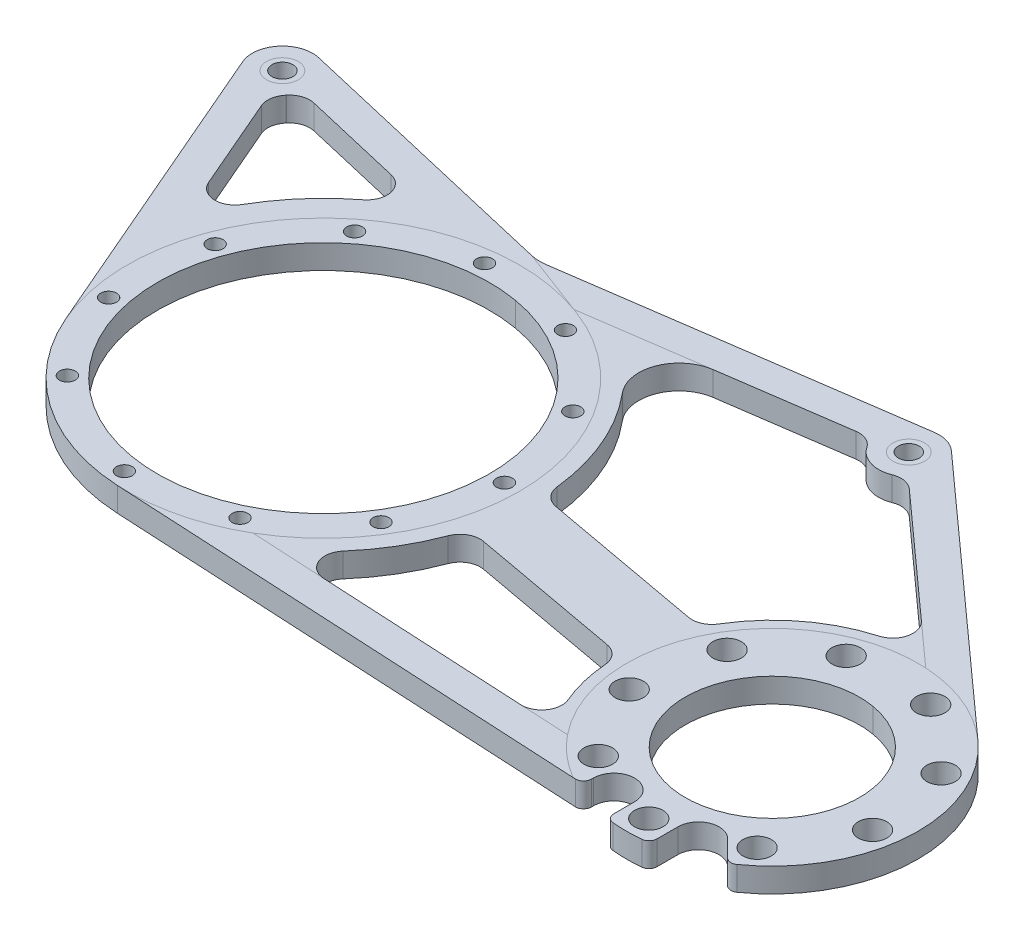
SolidWorks part; units mm, degrees
material "6061-T6 (SS)"
ref_plane "X-Y Datum" through (0, 0, 0) normal (0, 0, 1) x (1, 0, 0)
ref_plane "X-Z Datum" through (0, 0, 0) normal (0, 1, 0) x (1, 0, 0)
ref_plane "Y-Z Datum" through (0, 0, 0) normal (1, 0, 0) x (0, 0, -1)
sketch "Sketch2" plane through (0, 31.3819, 0) normal (0, 1, 0) x (1, 0, 0)
  line L0 (-693.7583, -176.702) -> (-693.7583, -183.2747) construction
  line L1 (-680.0808, -183.2747) -> (-680.0808, -176.702) construction
  line L2 (-668.9846, -172.1058) -> (-663.7197, -177.3707) construction
  line L3 (-693.7583, -176.702) -> (-693.7583, -183.2747)
  line L4 (-680.0808, -183.2747) -> (-680.0808, -176.702)
  line L5 (-668.9846, -172.1058) -> (-663.7197, -177.3707)
  line L6 (-966.641, -0.354) -> (-738.041, -0.354)
  line L7 (-727.7656, -5.5904) -> (-649.7224, -113.0358)
  line L9 (-977.8288, -19.0644) -> (-913.2312, -139.3061)
  line L10 (-706.7583, -177.279) -> (-706.7583, -176.702) construction
  line L11 (-706.7583, -177.279) -> (-706.7583, -176.702)
  line L12 (-861.9259, -171.8334) -> (-709.2983, -179.819)
  line L13 (-858.691, -110.0055) -> (-686.9195, -140.054) construction
  line L14 (-972.26, -24.9963) -> (-955.4664, -39.59) construction
  line L15 (-941.4162, -26.937) -> (-954.1775, -8.712) construction
  line L16 (-751.1929, -14.159) -> (-755.4346, -35.9995) construction
  line L17 (-737.4517, -41.8408) -> (-728.049, -21.6768) construction
  line L18 (-972.26, -24.9963) -> (-955.4664, -39.59)
  line L19 (-941.4162, -26.937) -> (-954.1775, -8.712)
  line L20 (-751.1929, -14.159) -> (-755.4346, -35.9995)
  line L21 (-737.4517, -41.8408) -> (-728.049, -21.6768)
  line L22 (-949.2186, -22.8753) -> (-746.0843, -28.2904)
  line L23 (-739.7146, -30.7335) -> (-656.1751, -105.8723)
  line L24 (-957.9647, -36.1729) -> (-915.5404, -134.527)
  arc A0 (-710.607, -179.4559) -> (-706.7583, -177.279) centre (-709.2983, -177.279) ccw construction
  arc A1 (-693.7583, -176.702) -> (-706.7583, -176.702) centre (-700.2583, -176.702) ccw construction
  arc A2 (-693.7583, -183.2747) -> (-691.4697, -185.8023) centre (-691.2183, -183.2747) ccw construction
  arc A3 (-691.4697, -185.8023) -> (-682.3694, -185.8023) centre (-686.9195, -140.054) ccw construction
  arc A4 (-682.3694, -185.8023) -> (-680.0808, -183.2747) centre (-682.6208, -183.2747) ccw construction
  arc A5 (-668.9846, -172.1058) -> (-680.0808, -176.702) centre (-673.5808, -176.702) ccw construction
  arc A6 (-663.7197, -177.3707) -> (-660.4619, -177.6519) centre (-661.9236, -175.5746) ccw construction
  arc A7 (-660.4619, -177.6519) -> (-710.607, -179.4559) centre (-686.9195, -140.054) ccw construction
  circle A8 centre (-858.691, -110.0055) radius 52.3875 construction
  circle A9 centre (-858.691, -110.0055) radius 61.9125 construction
  circle A10 centre (-738.041, -13.054) radius 12.7 construction
  circle A11 centre (-966.641, -13.054) radius 12.7 construction
  arc A12 (-710.607, -179.4559) -> (-706.7583, -177.279) centre (-709.2983, -177.279) ccw
  arc A13 (-693.7583, -176.702) -> (-706.7583, -176.702) centre (-700.2583, -176.702) ccw
  arc A14 (-693.7583, -183.2747) -> (-691.4697, -185.8023) centre (-691.2183, -183.2747) ccw
  arc A15 (-691.4697, -185.8023) -> (-682.3694, -185.8023) centre (-686.9195, -140.054) ccw
  arc A16 (-682.3694, -185.8023) -> (-680.0808, -183.2747) centre (-682.6208, -183.2747) ccw
  arc A17 (-668.9846, -172.1058) -> (-680.0808, -176.702) centre (-673.5808, -176.702) ccw
  arc A18 (-663.7197, -177.3707) -> (-660.4619, -177.6519) centre (-661.9236, -175.5746) ccw
  arc A19 (-660.4619, -177.6519) -> (-710.607, -179.4559) centre (-686.9195, -140.054) ccw
  circle A20 centre (-858.691, -110.0055) radius 52.3875
  circle A21 centre (-858.691, -110.0055) radius 61.9125
  circle A22 centre (-738.041, -13.054) radius 12.7
  circle A23 centre (-966.641, -13.054) radius 12.7
  circle A31 centre (-864.6648, -166.8424) radius 2.5 construction
  circle A39 centre (-864.6648, -166.8424) radius 2.5
  circle A40 centre (-686.9195, -140.054) radius 27.4955 construction
  circle A41 centre (-686.9195, -140.054) radius 27.4955
  circle A42 centre (-711.9883, -169.9297) radius 4.5 construction
  circle A43 centre (-725.3271, -146.8263) radius 4.5 construction
  circle A44 centre (-720.6945, -120.554) radius 4.5 construction
  circle A45 centre (-700.2583, -103.406) radius 4.5 construction
  circle A46 centre (-673.5808, -103.406) radius 4.5 construction
  circle A47 centre (-653.1446, -120.554) radius 4.5 construction
  circle A48 centre (-648.512, -146.8263) radius 4.5 construction
  circle A49 centre (-661.8508, -169.9297) radius 4.5 construction
  circle A50 centre (-686.9195, -179.054) radius 4.5 construction
  circle A51 centre (-711.9883, -169.9297) radius 4.5
  circle A52 centre (-725.3271, -146.8263) radius 4.5
  circle A53 centre (-720.6945, -120.554) radius 4.5
  circle A54 centre (-700.2583, -103.406) radius 4.5
  circle A55 centre (-673.5808, -103.406) radius 4.5
  circle A56 centre (-653.1446, -120.554) radius 4.5
  circle A57 centre (-648.512, -146.8263) radius 4.5
  circle A58 centre (-661.8508, -169.9297) radius 4.5
  circle A59 centre (-686.9195, -179.054) radius 4.5
  circle A60 centre (-966.641, -13.054) radius 3.3
  circle A61 centre (-738.041, -13.054) radius 3.3
  arc A62 (-955.4664, -39.59) -> (-941.4162, -26.937) centre (-949.2186, -32.4003) ccw construction
  arc A63 (-749.3237, -37.1863) -> (-742.8448, -38.4445) centre (-746.0843, -37.8154) ccw construction
  arc A64 (-742.8448, -38.4445) -> (-749.3237, -37.1863) centre (-746.0843, -37.8154) ccw construction
  arc A65 (-755.4346, -35.9995) -> (-737.4517, -41.8408) centre (-746.0843, -37.8154) ccw construction
  arc A66 (-955.4664, -39.59) -> (-941.4162, -26.937) centre (-949.2186, -32.4003) ccw
  arc A67 (-749.3237, -37.1863) -> (-742.8448, -38.4445) centre (-746.0843, -37.8154) ccw
  arc A68 (-742.8448, -38.4445) -> (-749.3237, -37.1863) centre (-746.0843, -37.8154) ccw
  arc A69 (-755.4346, -35.9995) -> (-737.4517, -41.8408) centre (-746.0843, -37.8154) ccw
  circle A70 centre (-949.2186, -32.4003) radius 3.3
  circle A71 centre (-949.2186, -32.4003) radius 9.525
  circle A72 centre (-746.0843, -37.8154) radius 9.525
  point P94 (-949.2186, -32.4003)
  dimension "D1" = 6.6
  dimension "D2" = 6.6
  dimension "D3" = 6.6
extrude "Boss-Extrude1" add sketch "Sketch2" along normal blind 7.62 contours A21 A39 A20 | A18 A19 A12 L11 A13 L3 A14 A15 A16 L4 A17 L5 A59 A58 A57 A56 A55 A54 A53 A52 A51 A41 | L13 A21 L12 A12 A19 | A21 L13 A19 L23 L21 A69 L20 L22 L19 A66 L18 L24 | A69 A72 A68 A67 | A72 L22 L20 | A72 L21 L23 | A71 L24 L18 | A71 L19 L22 | A71 A66 L22 A70 region at (-700.2583, 31.3819, 168.9016) region at (-773.051, 31.3819, 154.3682) region at (-890.9045, 31.3819, 160.8157) region at (-806.8861, 31.3819, 67.2042) region at (-956.9478, 31.3819, 38.0512) region at (-736.2382, 31.3819, 35.8095) region at (-956.6903, 31.3819, 37.8629) region at (-748.9437, 31.3819, 46.6182) region at (-752.4763, 31.3819, 29.8585) region at (-944.5842, 31.3819, 23.8004)
sketch "Sketch3" plane through (0, 31.3819, 0) normal (0, -1, 0) x (1, 0, 0)
  line L1 (-949.2186, 22.8753) -> (-746.0843, 28.2904) construction
  line L5 (-861.9259, 171.8334) -> (-709.2983, 179.819) construction
  line L6 (-977.8288, 19.0644) -> (-913.2312, 139.3061) construction
  line L7 (-727.7656, 5.5904) -> (-649.7224, 113.0358) construction
  line L13 (-751.1929, 14.159) -> (-755.4346, 35.9995) construction
  line L16 (-966.641, 0.354) -> (-738.041, 0.354) construction
  line L19 (-663.7197, 177.3707) -> (-668.9846, 172.1058)
  line L20 (-680.0808, 176.702) -> (-680.0808, 183.2747)
  line L21 (-693.7583, 183.2747) -> (-693.7583, 176.702)
  line L22 (-706.7583, 176.702) -> (-706.7583, 177.279)
  line L23 (-663.7197, 177.3707) -> (-668.9846, 172.1058)
  line L24 (-680.0808, 176.702) -> (-680.0808, 183.2747)
  line L25 (-693.7583, 183.2747) -> (-693.7583, 176.702)
  line L26 (-706.7583, 176.702) -> (-706.7583, 177.279)
  line L28 (-861.9259, 171.8334) -> (-709.2983, 179.819)
  line L29 (-977.8288, 19.0644) -> (-913.2312, 139.3061)
  line L30 (-727.7656, 5.5904) -> (-649.7224, 113.0358)
  line L31 (-966.641, 0.354) -> (-738.041, 0.354)
  line L34 (-737.4517, 41.8408) -> (-728.049, 21.6768) construction
  line L35 (-972.26, 24.9963) -> (-955.4664, 39.59) construction
  line L36 (-947.0539, 23.1246) -> (-856.9722, 44.1471)
  line L37 (-856.9722, 44.1471) -> (-747.4408, 28.3875)
  line L44 (-941.4162, 26.937) -> (-954.1775, 8.712) construction
  line L45 (-957.9647, 36.1729) -> (-915.5404, 134.527) construction
  line L46 (-739.7146, 30.7335) -> (-656.1751, 105.8723) construction
  line L47 (-861.9259, 171.8334) -> (-709.2983, 179.819)
  line L48 (-977.8288, 19.0644) -> (-913.2312, 139.3061)
  line L49 (-727.7656, 5.5904) -> (-649.7224, 113.0358)
  line L50 (-966.641, 0.354) -> (-738.041, 0.354)
  line L51 (-949.2186, 22.8753) -> (-746.0843, 28.2904)
  line L52 (-751.1929, 14.159) -> (-755.4346, 35.9995)
  line L53 (-737.4517, 41.8408) -> (-728.049, 21.6768)
  line L54 (-972.26, 24.9963) -> (-955.4664, 39.59)
  line L55 (-941.4162, 26.937) -> (-954.1775, 8.712)
  line L56 (-957.9647, 36.1729) -> (-915.5404, 134.527)
  line L57 (-739.7146, 30.7335) -> (-656.1751, 105.8723)
  arc A1 (-737.4517, 41.8408) -> (-755.4346, 35.9995) centre (-746.0843, 37.8154) ccw construction
  circle A3 centre (-966.641, 13.054) radius 12.7
  circle A5 centre (-966.641, 13.054) radius 12.7
  circle A7 centre (-738.041, 13.054) radius 12.7
  circle A9 centre (-738.041, 13.054) radius 12.7
  circle A11 centre (-858.691, 110.0055) radius 61.9125
  circle A13 centre (-858.691, 110.0055) radius 61.9125
  circle A15 centre (-858.691, 110.0055) radius 52.3875
  circle A17 centre (-858.691, 110.0055) radius 52.3875
  circle A19 centre (-686.9195, 140.054) radius 27.4955
  circle A21 centre (-686.9195, 140.054) radius 27.4955
  circle A23 centre (-864.6648, 166.8424) radius 2.5
  circle A25 centre (-864.6648, 166.8424) radius 2.5
  circle A51 centre (-720.6945, 120.554) radius 4.5
  circle A52 centre (-720.6945, 120.554) radius 4.5
  circle A68 centre (-725.3271, 146.8263) radius 4.5
  circle A69 centre (-725.3271, 146.8263) radius 4.5
  circle A70 centre (-711.9883, 169.9297) radius 4.5
  circle A71 centre (-711.9883, 169.9297) radius 4.5
  circle A72 centre (-738.041, 13.054) radius 3.3
  circle A73 centre (-738.041, 13.054) radius 3.3
  circle A74 centre (-966.641, 13.054) radius 3.3
  circle A75 centre (-966.641, 13.054) radius 3.3
  circle A76 centre (-686.9195, 179.054) radius 4.5
  circle A77 centre (-686.9195, 179.054) radius 4.5
  circle A78 centre (-661.8508, 169.9297) radius 4.5
  circle A79 centre (-661.8508, 169.9297) radius 4.5
  circle A80 centre (-648.512, 146.8263) radius 4.5
  circle A81 centre (-648.512, 146.8263) radius 4.5
  circle A82 centre (-653.1446, 120.554) radius 4.5
  circle A83 centre (-653.1446, 120.554) radius 4.5
  circle A84 centre (-673.5808, 103.406) radius 4.5
  circle A85 centre (-673.5808, 103.406) radius 4.5
  circle A86 centre (-700.2583, 103.406) radius 4.5
  circle A87 centre (-700.2583, 103.406) radius 4.5
  arc A95 (-710.607, 179.4559) -> (-660.4619, 177.6519) centre (-686.9195, 140.054) ccw
  arc A96 (-660.4619, 177.6519) -> (-663.7197, 177.3707) centre (-661.9236, 175.5746) ccw
  arc A97 (-680.0808, 176.702) -> (-668.9846, 172.1058) centre (-673.5808, 176.702) ccw
  arc A98 (-680.0808, 183.2747) -> (-682.3694, 185.8023) centre (-682.6208, 183.2747) ccw
  arc A99 (-682.3694, 185.8023) -> (-691.4697, 185.8023) centre (-686.9195, 140.054) ccw
  arc A100 (-691.4697, 185.8023) -> (-693.7583, 183.2747) centre (-691.2183, 183.2747) ccw
  arc A101 (-706.7583, 176.702) -> (-693.7583, 176.702) centre (-700.2583, 176.702) ccw
  arc A102 (-706.7583, 177.279) -> (-710.607, 179.4559) centre (-709.2983, 177.279) ccw
  arc A103 (-710.607, 179.4559) -> (-660.4619, 177.6519) centre (-686.9195, 140.054) ccw
  arc A104 (-660.4619, 177.6519) -> (-663.7197, 177.3707) centre (-661.9236, 175.5746) ccw
  arc A105 (-680.0808, 176.702) -> (-668.9846, 172.1058) centre (-673.5808, 176.702) ccw
  arc A106 (-680.0808, 183.2747) -> (-682.3694, 185.8023) centre (-682.6208, 183.2747) ccw
  arc A107 (-682.3694, 185.8023) -> (-691.4697, 185.8023) centre (-686.9195, 140.054) ccw
  arc A108 (-691.4697, 185.8023) -> (-693.7583, 183.2747) centre (-691.2183, 183.2747) ccw
  arc A109 (-706.7583, 176.702) -> (-693.7583, 176.702) centre (-700.2583, 176.702) ccw
  arc A110 (-706.7583, 177.279) -> (-710.607, 179.4559) centre (-709.2983, 177.279) ccw
  circle A152 centre (-746.0843, 37.8154) radius 9.525
  circle A153 centre (-746.0843, 37.8154) radius 9.525
  circle A154 centre (-949.2186, 32.4003) radius 9.525
  circle A155 centre (-949.2186, 32.4003) radius 9.525
  circle A156 centre (-949.2186, 32.4003) radius 3.3
  circle A157 centre (-949.2186, 32.4003) radius 3.3
  arc A158 (-941.4162, 26.937) -> (-955.4664, 39.59) centre (-949.2186, 32.4003) ccw construction
  arc A159 (-742.8448, 38.4445) -> (-749.3237, 37.1863) centre (-746.0843, 37.8154) ccw
  arc A160 (-749.3237, 37.1863) -> (-742.8448, 38.4445) centre (-746.0843, 37.8154) ccw
  arc A161 (-742.8448, 38.4445) -> (-749.3237, 37.1863) centre (-746.0843, 37.8154) ccw
  arc A162 (-749.3237, 37.1863) -> (-742.8448, 38.4445) centre (-746.0843, 37.8154) ccw
  arc A163 (-737.4517, 41.8408) -> (-755.4346, 35.9995) centre (-746.0843, 37.8154) ccw
  arc A164 (-941.4162, 26.937) -> (-955.4664, 39.59) centre (-949.2186, 32.4003) ccw
  dimension "D24" = 0
  dimension "D25" = 0
  dimension "D26" = 90.0818
  dimension "D27" = 21.0225
  dimension "D1" = 0
  dimension "D2" = 0
  dimension "D3" = 0
  dimension "D4" = 0
  dimension "D5" = 0
  dimension "D6" = 0
  dimension "D14" = 0
  dimension "D15" = 0
  dimension "D16" = 0
  dimension "D17" = 0
  dimension "D18" = 0
  dimension "D19" = 0
  dimension "D20" = 0
  dimension "D21" = 0
  dimension "D22" = 0
  dimension "D23" = 0
  dimension "D52" = 0
  dimension "D53" = 0
  dimension "D54" = 0
  dimension "D55" = 0
ref_point "Point1"
ref_point "Point2"
ref_plane "Plane1" through (-858.691, 31.3819, 110.0055) normal (0.985, 0, 0.1723) x (0.1723, 0, -0.985)
ref_plane "Plane2" through (-686.9195, 31.3819, 140.054) normal (-0.985, 0, -0.1723) x (-0.1723, 0, 0.985)
split line "Split Line1"
split line "Split Line2"
ref_axis "Axis1" through (-858.691, 39.0019, 110.0055) along (0, -1, 0)
ref_axis "Axis2" through (-686.9195, 39.0019, 140.054) along (0, -1, 0)
extrude "Cut-Extrude1" cut sketch "Sketch3" against normal through all contours L36 L55 L51 L52 L37 | A155 L51 L55 L36 | A153 L37 L52 L51 region at (-751.5495, 31.3819, 28.5688) region at (-850.6911, 31.3819, 31.7926) region at (-945.2616, 31.3819, 23.2848)
fillet "Fillet2" radius 12.7 1 edges at (-856.9722, 35.1919, 44.1471)
sketch "Sketch4" plane through (0, 31.3819, 0) normal (0, -1, 0) x (1, 0, 0)
  line L0 (-861.9259, 171.8334) -> (-709.2983, 179.819) construction
  line L1 (-727.7656, 5.5904) -> (-649.7224, 113.0358) construction
  line L2 (-977.8288, 19.0644) -> (-913.2312, 139.3061) construction
  line L4 (-706.7583, 176.702) -> (-706.7583, 177.279)
  line L5 (-663.7197, 177.3707) -> (-668.9846, 172.1058)
  line L6 (-680.0808, 176.702) -> (-680.0808, 183.2747)
  line L7 (-693.7583, 183.2747) -> (-693.7583, 176.702)
  line L8 (-706.7583, 176.702) -> (-706.7583, 177.279)
  line L9 (-663.7197, 177.3707) -> (-668.9846, 172.1058)
  line L10 (-680.0808, 176.702) -> (-680.0808, 183.2747)
  line L11 (-693.7583, 183.2747) -> (-693.7583, 176.702)
  line L13 (-966.641, 0.354) -> (-738.041, 0.354) construction
  line L14 (-861.9259, 171.8334) -> (-709.2983, 179.819)
  line L15 (-727.7656, 5.5904) -> (-649.7224, 113.0358)
  line L16 (-977.8288, 19.0644) -> (-913.2312, 139.3061)
  line L17 (-861.9259, 171.8334) -> (-709.2983, 179.819) construction
  line L19 (-966.641, 0.354) -> (-738.041, 0.354)
  line L20 (-924.6037, 87.863) -> (-948.1369, 33.3048)
  line L21 (-948.1369, 33.3048) -> (-888.5504, 47.2106)
  line L22 (-732.3805, 168.4374) -> (-812.7818, 164.2308) construction
  line L23 (-812.7818, 164.2308) -> (-733.9678, 114.3873) construction
  line L24 (-799.833, 147.0258) -> (-703.8013, 86.2934) construction
  line L25 (-703.8013, 86.2934) -> (-794.9695, 82.1785) construction
  line L26 (-824.108, 49.6832) -> (-755.4008, 39.7974) construction
  line L27 (-798.9847, 74.3695) -> (-701.5009, 78.7695) construction
  line L28 (-701.5009, 78.7695) -> (-739.4428, 44.643) construction
  line L29 (-977.8288, 19.0644) -> (-913.2312, 139.3061) construction
  line L30 (-727.7656, 5.5904) -> (-649.7224, 113.0358) construction
  line L31 (-966.641, 0.354) -> (-738.041, 0.354) construction
  line L32 (-663.7197, 177.3707) -> (-668.9846, 172.1058)
  line L33 (-680.0808, 176.702) -> (-680.0808, 183.2747)
  line L34 (-693.7583, 183.2747) -> (-693.7583, 176.702)
  line L35 (-706.7583, 176.702) -> (-706.7583, 177.279)
  line L36 (-663.7197, 177.3707) -> (-668.9846, 172.1058)
  line L37 (-680.0808, 176.702) -> (-680.0808, 183.2747)
  line L38 (-693.7583, 183.2747) -> (-693.7583, 176.702)
  line L39 (-706.7583, 176.702) -> (-706.7583, 177.279)
  line L40 (-949.2186, 22.8753) -> (-746.0843, 28.2904) construction
  line L41 (-751.1929, 14.159) -> (-755.4346, 35.9995) construction
  line L42 (-737.4517, 41.8408) -> (-728.049, 21.6768) construction
  line L43 (-972.26, 24.9963) -> (-955.4664, 39.59) construction
  line L44 (-941.4162, 26.937) -> (-954.1775, 8.712) construction
  line L45 (-957.9647, 36.1729) -> (-915.5404, 134.527) construction
  line L46 (-739.7146, 30.7335) -> (-656.1751, 105.8723) construction
  line L47 (-861.9259, 171.8334) -> (-709.2983, 179.819)
  line L48 (-977.8288, 19.0644) -> (-913.2312, 139.3061)
  line L49 (-727.7656, 5.5904) -> (-649.7224, 113.0358)
  line L50 (-966.641, 0.354) -> (-738.041, 0.354)
  line L51 (-949.2186, 22.8753) -> (-746.0843, 28.2904)
  line L52 (-751.1929, 14.159) -> (-755.4346, 35.9995)
  line L53 (-737.4517, 41.8408) -> (-728.049, 21.6768)
  line L54 (-972.26, 24.9963) -> (-955.4664, 39.59)
  line L55 (-941.4162, 26.937) -> (-954.1775, 8.712)
  line L56 (-957.9647, 36.1729) -> (-915.5404, 134.527)
  line L57 (-739.7146, 30.7335) -> (-656.1751, 105.8723)
  line L58 (-947.0539, 23.1246) -> (-859.3005, 43.6037) construction
  line L60 (-854.6056, 43.8066) -> (-747.4408, 28.3875) construction
  circle A1 centre (-858.691, 110.0055) radius 52.3875
  circle A2 centre (-858.691, 110.0055) radius 52.3875
  circle A3 centre (-858.691, 110.0055) radius 61.9125
  circle A4 centre (-858.691, 110.0055) radius 61.9125
  circle A5 centre (-738.041, 13.054) radius 12.7
  circle A6 centre (-738.041, 13.054) radius 12.7
  circle A7 centre (-966.641, 13.054) radius 12.7
  circle A8 centre (-966.641, 13.054) radius 12.7
  circle A17 centre (-864.6648, 166.8424) radius 2.5
  circle A18 centre (-864.6648, 166.8424) radius 2.5
  circle A19 centre (-686.9195, 140.054) radius 27.4955
  circle A20 centre (-686.9195, 140.054) radius 27.4955
  circle A21 centre (-725.3271, 146.8263) radius 4.5
  circle A22 centre (-725.3271, 146.8263) radius 4.5
  circle A23 centre (-720.6945, 120.554) radius 4.5
  circle A24 centre (-720.6945, 120.554) radius 4.5
  circle A31 centre (-661.8508, 169.9297) radius 4.5
  circle A32 centre (-661.8508, 169.9297) radius 4.5
  circle A33 centre (-686.9195, 179.054) radius 4.5
  circle A34 centre (-686.9195, 179.054) radius 4.5
  circle A35 centre (-966.641, 13.054) radius 3.3
  circle A36 centre (-966.641, 13.054) radius 3.3
  circle A37 centre (-738.041, 13.054) radius 3.3
  circle A38 centre (-738.041, 13.054) radius 3.3
  circle A39 centre (-711.9883, 169.9297) radius 4.5
  circle A40 centre (-711.9883, 169.9297) radius 4.5
  circle A41 centre (-700.2583, 103.406) radius 4.5
  circle A42 centre (-700.2583, 103.406) radius 4.5
  circle A43 centre (-673.5808, 103.406) radius 4.5
  circle A44 centre (-673.5808, 103.406) radius 4.5
  circle A45 centre (-653.1446, 120.554) radius 4.5
  circle A46 centre (-653.1446, 120.554) radius 4.5
  circle A47 centre (-648.512, 146.8263) radius 4.5
  circle A48 centre (-648.512, 146.8263) radius 4.5
  arc A49 (-888.5504, 47.2106) -> (-924.6037, 87.863) centre (-858.691, 110.0055) cw
  arc A50 (-732.3805, 168.4374) -> (-733.9678, 114.3873) centre (-686.9195, 140.054) ccw construction
  arc A51 (-799.833, 147.0258) -> (-794.9695, 82.1785) centre (-858.691, 110.0055) cw construction
  arc A52 (-824.108, 49.6832) -> (-798.9847, 74.3695) centre (-858.691, 110.0055) ccw construction
  arc A53 (-737.4517, 41.8408) -> (-755.4346, 35.9995) centre (-746.0843, 37.8154) ccw construction
  circle A54 centre (-966.641, 13.054) radius 12.7
  circle A55 centre (-966.641, 13.054) radius 12.7
  arc A56 (-706.7583, 177.279) -> (-710.607, 179.4559) centre (-709.2983, 177.279) ccw
  arc A57 (-710.607, 179.4559) -> (-660.4619, 177.6519) centre (-686.9195, 140.054) ccw
  arc A58 (-660.4619, 177.6519) -> (-663.7197, 177.3707) centre (-661.9236, 175.5746) ccw
  arc A59 (-680.0808, 176.702) -> (-668.9846, 172.1058) centre (-673.5808, 176.702) ccw
  arc A60 (-680.0808, 183.2747) -> (-682.3694, 185.8023) centre (-682.6208, 183.2747) ccw
  arc A61 (-682.3694, 185.8023) -> (-691.4697, 185.8023) centre (-686.9195, 140.054) ccw
  arc A62 (-691.4697, 185.8023) -> (-693.7583, 183.2747) centre (-691.2183, 183.2747) ccw
  arc A63 (-706.7583, 176.702) -> (-693.7583, 176.702) centre (-700.2583, 176.702) ccw
  arc A64 (-706.7583, 177.279) -> (-710.607, 179.4559) centre (-709.2983, 177.279) ccw
  arc A65 (-710.607, 179.4559) -> (-660.4619, 177.6519) centre (-686.9195, 140.054) ccw
  arc A66 (-660.4619, 177.6519) -> (-663.7197, 177.3707) centre (-661.9236, 175.5746) ccw
  arc A67 (-680.0808, 176.702) -> (-668.9846, 172.1058) centre (-673.5808, 176.702) ccw
  arc A68 (-680.0808, 183.2747) -> (-682.3694, 185.8023) centre (-682.6208, 183.2747) ccw
  arc A69 (-682.3694, 185.8023) -> (-691.4697, 185.8023) centre (-686.9195, 140.054) ccw
  arc A70 (-691.4697, 185.8023) -> (-693.7583, 183.2747) centre (-691.2183, 183.2747) ccw
  arc A71 (-706.7583, 176.702) -> (-693.7583, 176.702) centre (-700.2583, 176.702) ccw
  circle A72 centre (-738.041, 13.054) radius 12.7
  circle A73 centre (-738.041, 13.054) radius 12.7
  circle A74 centre (-858.691, 110.0055) radius 61.9125
  circle A75 centre (-858.691, 110.0055) radius 61.9125
  circle A76 centre (-858.691, 110.0055) radius 52.3875
  circle A77 centre (-858.691, 110.0055) radius 52.3875
  circle A78 centre (-686.9195, 140.054) radius 27.4955
  circle A79 centre (-686.9195, 140.054) radius 27.4955
  circle A80 centre (-864.6648, 166.8424) radius 2.5
  circle A81 centre (-864.6648, 166.8424) radius 2.5
  circle A96 centre (-720.6945, 120.554) radius 4.5
  circle A97 centre (-720.6945, 120.554) radius 4.5
  circle A98 centre (-725.3271, 146.8263) radius 4.5
  circle A99 centre (-725.3271, 146.8263) radius 4.5
  circle A100 centre (-711.9883, 169.9297) radius 4.5
  circle A101 centre (-711.9883, 169.9297) radius 4.5
  circle A102 centre (-738.041, 13.054) radius 3.3
  circle A103 centre (-738.041, 13.054) radius 3.3
  circle A104 centre (-966.641, 13.054) radius 3.3
  circle A105 centre (-966.641, 13.054) radius 3.3
  circle A106 centre (-686.9195, 179.054) radius 4.5
  circle A107 centre (-686.9195, 179.054) radius 4.5
  circle A108 centre (-661.8508, 169.9297) radius 4.5
  circle A109 centre (-661.8508, 169.9297) radius 4.5
  circle A110 centre (-648.512, 146.8263) radius 4.5
  circle A111 centre (-648.512, 146.8263) radius 4.5
  circle A112 centre (-653.1446, 120.554) radius 4.5
  circle A113 centre (-653.1446, 120.554) radius 4.5
  circle A114 centre (-673.5808, 103.406) radius 4.5
  circle A115 centre (-673.5808, 103.406) radius 4.5
  circle A116 centre (-700.2583, 103.406) radius 4.5
  circle A117 centre (-700.2583, 103.406) radius 4.5
  circle A118 centre (-746.0843, 37.8154) radius 9.525
  circle A119 centre (-746.0843, 37.8154) radius 9.525
  circle A120 centre (-949.2186, 32.4003) radius 9.525
  circle A121 centre (-949.2186, 32.4003) radius 9.525
  circle A122 centre (-949.2186, 32.4003) radius 3.3
  circle A123 centre (-949.2186, 32.4003) radius 3.3
  arc A124 (-941.4162, 26.937) -> (-955.4664, 39.59) centre (-949.2186, 32.4003) ccw construction
  arc A125 (-742.8448, 38.4445) -> (-749.3237, 37.1863) centre (-746.0843, 37.8154) ccw
  arc A126 (-749.3237, 37.1863) -> (-742.8448, 38.4445) centre (-746.0843, 37.8154) ccw
  arc A127 (-742.8448, 38.4445) -> (-749.3237, 37.1863) centre (-746.0843, 37.8154) ccw
  arc A128 (-749.3237, 37.1863) -> (-742.8448, 38.4445) centre (-746.0843, 37.8154) ccw
  arc A129 (-737.4517, 41.8408) -> (-755.4346, 35.9995) centre (-746.0843, 37.8154) ccw
  arc A130 (-941.4162, 26.937) -> (-955.4664, 39.59) centre (-949.2186, 32.4003) ccw
  arc A135 (-710.607, 179.4559) -> (-660.4619, 177.6519) centre (-686.9195, 140.054) ccw
  arc A136 (-660.4619, 177.6519) -> (-663.7197, 177.3707) centre (-661.9236, 175.5746) ccw
  arc A137 (-680.0808, 176.702) -> (-668.9846, 172.1058) centre (-673.5808, 176.702) ccw
  arc A138 (-680.0808, 183.2747) -> (-682.3694, 185.8023) centre (-682.6208, 183.2747) ccw
  arc A139 (-682.3694, 185.8023) -> (-691.4697, 185.8023) centre (-686.9195, 140.054) ccw
  arc A140 (-691.4697, 185.8023) -> (-693.7583, 183.2747) centre (-691.2183, 183.2747) ccw
  arc A141 (-706.7583, 176.702) -> (-693.7583, 176.702) centre (-700.2583, 176.702) ccw
  arc A142 (-706.7583, 177.279) -> (-710.607, 179.4559) centre (-709.2983, 177.279) ccw
  arc A143 (-710.607, 179.4559) -> (-660.4619, 177.6519) centre (-686.9195, 140.054) ccw
  arc A144 (-660.4619, 177.6519) -> (-663.7197, 177.3707) centre (-661.9236, 175.5746) ccw
  arc A145 (-680.0808, 176.702) -> (-668.9846, 172.1058) centre (-673.5808, 176.702) ccw
  arc A146 (-680.0808, 183.2747) -> (-682.3694, 185.8023) centre (-682.6208, 183.2747) ccw
  arc A147 (-682.3694, 185.8023) -> (-691.4697, 185.8023) centre (-686.9195, 140.054) ccw
  arc A148 (-691.4697, 185.8023) -> (-693.7583, 183.2747) centre (-691.2183, 183.2747) ccw
  arc A149 (-706.7583, 176.702) -> (-693.7583, 176.702) centre (-700.2583, 176.702) ccw
  arc A150 (-706.7583, 177.279) -> (-710.607, 179.4559) centre (-709.2983, 177.279) ccw
  dimension "D26" = 7.62
  dimension "D29" = 7.62
  dimension "D30" = 7.62
  dimension "D35" = 0
  dimension "D39" = 7.62
  dimension "D27" = 0
  dimension "D28" = 0
  dimension "D31" = 10.16
  dimension "D32" = 7.62
  dimension "D33" = 93.2524
  dimension "D34" = 49.8435
  dimension "D36" = 91.1683
  dimension "D37" = 4.1149
  dimension "D38" = 10.16
  dimension "D40" = 7.62
  dimension "D67" = 10.16
  dimension "D68" = 10.16
  dimension "D69" = 10.16
  dimension "D1" = 0
  dimension "D2" = 0
  dimension "D3" = 0
  dimension "D4" = 0
  dimension "D9" = 0
  dimension "D10" = 0
  dimension "D11" = 0
  dimension "D12" = 0
  dimension "D16" = 0
  dimension "D17" = 0
  dimension "D18" = 0
  dimension "D19" = 0
  dimension "D20" = 0
  dimension "D21" = 0
  dimension "D22" = 0
  dimension "D23" = 0
  dimension "D24" = 0
  dimension "D25" = 0
  dimension "D41" = 0
  dimension "D42" = 0
  dimension "D43" = 0
  dimension "D51" = 0
  dimension "D52" = 0
  dimension "D53" = 0
  dimension "D54" = 0
  dimension "D55" = 0
  dimension "D56" = 0
  dimension "D57" = 0
  dimension "D58" = 0
  dimension "D59" = 0
  dimension "D60" = 0
  dimension "D61" = 0
  dimension "D62" = 0
  dimension "D63" = 0
  dimension "D64" = 0
  dimension "D65" = 0
  dimension "D66" = 0
extrude "Cut-Extrude2" cut sketch "Sketch4" against normal through all contours L21 A49 L20 A8 | A52 L26 A6 L28 L27 | L24 A51 L25 | A50 L22 L23 region at (-829.4195, 31.3819, 24.9298) region at (-921.8341, 31.3819, 54.9859)
fillet "Fillet3" [suppressed] radius 6.604
split line "Split Line3"
sketch "Sketch2<4>" plane through (0, 31.3819, 0) normal (0, 1, 0) x (1, 0, 0) same geometry as "Sketch2"
pattern_circular "CirPattern2" count 11 every 32 about axis through (-858.691, 39.0019, 110.0055) along (0, -1, 0) reverse direction yes of face at (-867.1648, 39.0019, 166.8424)
sketch "Sketch5" plane through (0, 39.0019, 0) normal (0, 1, 0) x (1, 0, 0)
  circle A0 centre (-949.2186, -32.4003) radius 5
  circle A1 centre (-746.0843, -37.8154) radius 5
  dimension "D1" = 10
split line "Split Line4"
sketch "Sketch6" [suppressed] plane through (0, 31.3819, 0) normal (0, -1, 0) x (1, 0, 0)
  line L0 (-743.6056, 167.8501) -> (-792.0577, 165.3151) construction
  line L1 (-724.7926, 85.346) -> (-785.1492, 82.6217) construction
  line L2 (-724.7926, 85.346) -> (-785.1492, 82.6217)
  line L3 (-791.5915, 128.2378) -> (-796.8267, 141.9391)
  line L4 (-743.6056, 167.8501) -> (-781.2512, 165.8805)
  line L5 (-781.2512, 165.8805) -> (-792.0577, 165.3151)
  arc A0 (-791.8001, 91.022) -> (-791.5915, 128.2378) centre (-858.691, 110.0055) ccw construction
  arc A1 (-791.8001, 91.022) -> (-791.5915, 128.2378) centre (-858.691, 110.0055) ccw
  circle A2 centre (-780.3284, 148.243) radius 17.6616 construction
  circle A3 centre (-744.0706, 102.1866) radius 14.9639 construction
  arc A4 (-737.0797, 158.9293) -> (-739.7578, 131.0856) centre (-686.9195, 140.054) ccw construction
  arc A5 (-724.7926, 85.346) -> (-721.5605, 97.5247) centre (-725.0904, 91.9433) ccw construction
  arc A6 (-737.0797, 158.9293) -> (-743.6056, 167.8501) centre (-743.2606, 161.2551) ccw construction
  arc A7 (-737.0797, 158.9293) -> (-739.7578, 131.0856) centre (-686.9195, 140.054) ccw
  arc A8 (-737.0797, 158.9293) -> (-743.6056, 167.8501) centre (-743.2606, 161.2551) ccw
  arc A9 (-724.7926, 85.346) -> (-721.5605, 97.5247) centre (-725.0904, 91.9433) ccw
  arc A10 (-791.8001, 91.022) -> (-785.1492, 82.6217) centre (-785.447, 89.219) ccw construction
  arc A11 (-791.8001, 91.022) -> (-785.1492, 82.6217) centre (-785.447, 89.219) ccw
  arc A13 (-739.7578, 131.0856) -> (-731.5964, 110.4517) centre (-686.9195, 140.054) ccw
  arc A14 (-721.5605, 97.5247) -> (-731.5964, 110.4517) centre (-640.5401, 170.7843) cw
  arc A15 (-792.0577, 165.3151) -> (-798.1017, 160.3912) centre (-791.7127, 158.7201) ccw
  arc A17 (-792.0577, 165.3151) -> (-795.2425, 153.1386) centre (-791.7127, 158.7201) ccw construction
  arc A18 (-798.1017, 160.3912) -> (-796.8267, 141.9391) centre (-767.2093, 153.2558) ccw
  dimension "D3" = 31.7058
  dimension "D1" = 11.2631
  dimension "D2" = 22.5101
extrude "Cut-Extrude3" [suppressed] cut sketch "Sketch6" against normal through all
sketch "Sketch7" plane through (0, 31.3819, 0) normal (0, -1, 0) x (1, 0, 0)
  line L0 (-859.3005, 43.6037) -> (-836.8375, 52.0781)
  arc A0 (-915.5404, 134.527) -> (-861.9259, 171.8334) centre (-858.691, 110.0055) ccw construction
split line "Split Line5"
sketch "Sketch8" plane through (0, 39.0019, 0) normal (0, 1, 0) x (1, 0, 0)
  line L0 (-859.3005, -43.6037) -> (-836.8375, -52.0781) construction
  line L1 (-859.3005, -43.6037) -> (-836.8375, -52.0781)
  line L2 (-732.3805, -168.4374) -> (-812.7818, -164.2308) construction
  line L3 (-824.108, -49.6832) -> (-755.4008, -39.7974) construction
  line L4 (-701.5009, -78.7695) -> (-739.4428, -44.643) construction
  line L5 (-732.3805, -168.4374) -> (-812.7818, -164.2308)
  line L6 (-824.108, -49.6832) -> (-755.4008, -39.7974)
  line L7 (-709.5634, -179.8051) -> (-709.2983, -179.819)
  line L8 (-668.9846, -172.1058) -> (-663.7197, -177.3707)
  line L9 (-680.0808, -183.2747) -> (-680.0808, -176.702)
  line L10 (-693.7583, -176.702) -> (-693.7583, -183.2747)
  line L11 (-706.7583, -177.279) -> (-706.7583, -176.702)
  line L12 (-709.5634, -179.8051) -> (-709.2983, -179.819)
  line L13 (-668.9846, -172.1058) -> (-663.7197, -177.3707)
  line L14 (-680.0808, -183.2747) -> (-680.0808, -176.702)
  line L15 (-693.7583, -176.702) -> (-693.7583, -183.2747)
  line L16 (-706.7583, -177.279) -> (-706.7583, -176.702)
  line L17 (-701.5009, -78.7695) -> (-739.4428, -44.643)
  line L18 (-701.5009, -78.7695) -> (-684.402, -94.149)
  line L19 (-824.108, -49.6832) -> (-837.9186, -51.6702)
  line L20 (-732.3805, -168.4374) -> (-722.6816, -168.9449)
  line L21 (-812.7818, -164.2308) -> (-827.4586, -163.4628)
  circle A0 centre (-746.0843, -37.8154) radius 9.525 construction
  circle A1 centre (-746.0843, -37.8154) radius 9.525 construction
  arc A2 (-739.4428, -44.643) -> (-755.4008, -39.7974) centre (-746.0843, -37.8154) cw
  arc A3 (-915.5404, -134.527) -> (-861.9259, -171.8334) centre (-858.691, -110.0055) ccw
  arc A4 (-836.8375, -52.0781) -> (-915.5404, -134.527) centre (-858.691, -110.0055) ccw
  arc A5 (-861.9259, -171.8334) -> (-836.8375, -52.0781) centre (-858.691, -110.0055) ccw
  arc A6 (-915.5404, -134.527) -> (-861.9259, -171.8334) centre (-858.691, -110.0055) ccw
  arc A7 (-836.8375, -52.0781) -> (-915.5404, -134.527) centre (-858.691, -110.0055) ccw
  arc A8 (-861.9259, -171.8334) -> (-836.8375, -52.0781) centre (-858.691, -110.0055) ccw
  arc A16 (-710.607, -179.4559) -> (-709.5634, -179.8051) centre (-709.2983, -177.279) ccw
  arc A17 (-656.1751, -105.8723) -> (-710.607, -179.4559) centre (-686.9195, -140.054) ccw
  arc A18 (-660.4619, -177.6519) -> (-656.1751, -105.8723) centre (-686.9195, -140.054) ccw
  arc A19 (-663.7197, -177.3707) -> (-660.4619, -177.6519) centre (-661.9236, -175.5746) ccw
  arc A20 (-668.9846, -172.1058) -> (-680.0808, -176.702) centre (-673.5808, -176.702) ccw
  arc A21 (-682.3694, -185.8023) -> (-680.0808, -183.2747) centre (-682.6208, -183.2747) ccw
  arc A22 (-691.4697, -185.8023) -> (-682.3694, -185.8023) centre (-686.9195, -140.054) ccw
  arc A23 (-693.7583, -183.2747) -> (-691.4697, -185.8023) centre (-691.2183, -183.2747) ccw
  arc A24 (-693.7583, -176.702) -> (-706.7583, -176.702) centre (-700.2583, -176.702) ccw
  arc A25 (-709.2983, -179.819) -> (-706.7583, -177.279) centre (-709.2983, -177.279) ccw
  arc A26 (-710.607, -179.4559) -> (-709.5634, -179.8051) centre (-709.2983, -177.279) ccw
  arc A27 (-656.1751, -105.8723) -> (-710.607, -179.4559) centre (-686.9195, -140.054) ccw
  arc A28 (-660.4619, -177.6519) -> (-656.1751, -105.8723) centre (-686.9195, -140.054) ccw
  arc A29 (-663.7197, -177.3707) -> (-660.4619, -177.6519) centre (-661.9236, -175.5746) ccw
  arc A30 (-668.9846, -172.1058) -> (-680.0808, -176.702) centre (-673.5808, -176.702) ccw
  arc A31 (-682.3694, -185.8023) -> (-680.0808, -183.2747) centre (-682.6208, -183.2747) ccw
  arc A32 (-691.4697, -185.8023) -> (-682.3694, -185.8023) centre (-686.9195, -140.054) ccw
  arc A33 (-693.7583, -183.2747) -> (-691.4697, -185.8023) centre (-691.2183, -183.2747) ccw
  arc A34 (-693.7583, -176.702) -> (-706.7583, -176.702) centre (-700.2583, -176.702) ccw
  arc A35 (-709.2983, -179.819) -> (-706.7583, -177.279) centre (-709.2983, -177.279) ccw
  dimension "D1" = 0
  dimension "D2" = 0
split line "Split Line6"
fillet "Fillet4" radius 6.3754 4 edges at (-940.1078, 35.1919, 35.1786) (-944.8714, 35.1919, 40.8754) (-888.5504, 35.1919, 47.2106) (-924.6037, 35.1919, 87.863)
sketch "Sketch9" plane through (0, 31.3819, 0) normal (0, -1, 0) x (1, 0, 0)
  line L8 (-732.3805, 168.4374) -> (-812.7818, 164.2308)
  line L9 (-722.6816, 168.9449) -> (-732.3805, 168.4374)
  line L10 (-701.5009, 78.7695) -> (-684.402, 94.149)
  line L11 (-739.4428, 44.643) -> (-701.5009, 78.7695)
  line L12 (-824.108, 49.6832) -> (-755.4008, 39.7974)
  line L13 (-837.9186, 51.6702) -> (-824.108, 49.6832)
  line L14 (-836.8375, 52.0781) -> (-837.9186, 51.6702)
  line L15 (-812.7818, 164.2308) -> (-827.4586, 163.4628)
  line L16 (-732.3805, 168.4374) -> (-812.7818, 164.2308)
  line L17 (-722.6816, 168.9449) -> (-732.3805, 168.4374)
  line L18 (-701.5009, 78.7695) -> (-684.402, 94.149)
  line L19 (-739.4428, 44.643) -> (-701.5009, 78.7695)
  line L20 (-824.108, 49.6832) -> (-755.4008, 39.7974)
  line L21 (-837.9186, 51.6702) -> (-824.108, 49.6832)
  line L22 (-836.8375, 52.0781) -> (-837.9186, 51.6702)
  line L23 (-812.7818, 164.2308) -> (-827.4586, 163.4628)
  arc A3 (-722.6816, 168.9449) -> (-684.402, 94.149) centre (-686.9195, 140.054) ccw
  arc A4 (-739.4428, 44.643) -> (-755.4008, 39.7974) centre (-746.0843, 37.8154) ccw
  arc A5 (-836.8375, 52.0781) -> (-827.4586, 163.4628) centre (-858.691, 110.0055) ccw
  arc A6 (-722.6816, 168.9449) -> (-684.402, 94.149) centre (-686.9195, 140.054) ccw
  arc A7 (-739.4428, 44.643) -> (-755.4008, 39.7974) centre (-746.0843, 37.8154) ccw
  arc A8 (-836.8375, 52.0781) -> (-827.4586, 163.4628) centre (-858.691, 110.0055) ccw
  dimension "D1" = 0
split line "Split Line7"
sketch "Sketch10" plane through (0, 31.3819, 0) normal (0, -1, 0) x (1, 0, 0)
  line L0 (-818.9129, 163.91) -> (-726.8377, 168.7274)
  line L1 (-732.3805, 168.4374) -> (-812.7818, 164.2308) construction
  line L2 (-837.9186, 51.6702) -> (-824.108, 49.6832) construction
  line L3 (-812.7818, 164.2308) -> (-827.4586, 163.4628) construction
  line L4 (-798.0516, 122.496) -> (-732.5518, 134.4586) construction
  line L5 (-794.2598, 128.3526) -> (-736.0569, 138.9824)
  line L6 (-791.745, 107.5102) -> (-731.1295, 118.5807)
  line L7 (-701.5009, 78.7695) -> (-684.402, 94.149) construction
  line L8 (-828.3256, 50.29) -> (-755.4008, 39.7974)
  line L9 (-739.4428, 44.643) -> (-687.9956, 90.9168)
  arc A0 (-828.3256, 50.29) -> (-791.745, 107.5102) centre (-858.691, 110.0055) ccw
  arc A1 (-731.1295, 118.5807) -> (-687.9956, 90.9168) centre (-686.9195, 140.054) ccw
  arc A2 (-818.9129, 163.91) -> (-794.2598, 128.3526) centre (-858.691, 110.0055) cw
  arc A3 (-835.0444, 47.3251) -> (-824.896, 167.8491) centre (-858.691, 110.0055) ccw
  arc A4 (-835.0444, 47.3251) -> (-824.896, 167.8491) centre (-858.691, 110.0055) ccw construction
  arc A5 (-836.8375, 52.0781) -> (-827.4586, 163.4628) centre (-858.691, 110.0055) ccw construction
  arc A6 (-722.6816, 168.9449) -> (-684.402, 94.149) centre (-686.9195, 140.054) ccw construction
  arc A7 (-726.8377, 168.7274) -> (-736.0569, 138.9824) centre (-686.9195, 140.054) ccw
  arc A8 (-725.1514, 170.9401) -> (-684.2281, 90.9787) centre (-686.9195, 140.054) ccw
  arc A9 (-725.1514, 170.9401) -> (-684.2281, 90.9787) centre (-686.9195, 140.054) ccw construction
  arc A10 (-755.4008, 39.7974) -> (-739.4428, 44.643) centre (-746.0843, 37.8154) cw
  arc A11 (-739.4428, 44.643) -> (-755.4008, 39.7974) centre (-746.0843, 37.8154) ccw construction
  dimension "D3" = 41.4139
  dimension "D4" = 34.2689
  dimension "D5" = 5.08
  dimension "D6" = 15.875
  dimension "D1" = 5.08
  dimension "D2" = 3.175
extrude "Cut-Extrude4" cut sketch "Sketch10" against normal through all contours L5 A7 L0 A2 | L9 A1 L6 A0 L8 A10
fillet "Fillet5" radius 6.3754 8 edges at (-687.9956, 35.1919, 90.9168) (-739.4428, 35.1919, 44.643) (-755.4008, 35.1919, 39.7974) (-731.1295, 35.1919, 118.5807) (-794.2598, 35.1919, 128.3526) (-736.0569, 35.1919, 138.9824) (-726.8377, 35.1919, 168.7274) (-818.9129, 35.1919, 163.91)
fillet "Fillet6" radius 6.3754 1 edges at (-791.745, 35.1919, 107.5102)
fillet "Fillet7" radius 12.7 1 edges at (-828.3256, 35.1919, 50.29)
sketch3d "3DSketch1"
  arc A3 (-738.3594, 31.3819, 168.1246) -> (-732.1581, 31.3819, 159.2658) centre (-738.0263, 31.3819, 161.7579) ccw construction
  arc A4 (-732.1581, 31.3819, 159.2658) -> (-735.6872, 31.3819, 146.1648) centre (-686.9195, 31.3819, 140.054) ccw
  arc A5 (-738.3594, 31.3819, 168.1246) -> (-732.1581, 31.3819, 159.2658) centre (-738.0263, 31.3819, 161.7579) ccw
  circle A6 centre (-752.529, 24.9199, 171.23) radius 5 construction
  circle A7 centre (-776.621, 24.7819, 169.8829) radius 5 construction
  point P6 (-686.9195, -17.7671, 140.054)
  point P14 (-738.0263, 37.7573, 161.7579)
  point P16 (-752.529, 29.9199, 171.23)
  point P18 (-776.621, 29.7819, 169.8829)
  point P23 (-738.0263, 37.7573, 161.7579)
  dimension "D2" = 10
  dimension "D3" = 10
  dimension "D4" = 39.9891
  dimension "D7" = 30.8815
  dimension "D1" = 24.13
  dimension "D5" = 18.4881
  dimension "D8" = 22.1218
  dimension "D9" = 10.8136
  dimension "D10" = 13.568
sketch "Sketch11" [suppressed] plane through (0, 31.3819, 0) normal (0, -1, 0) x (1, 0, 0)
  line L0 (-738.3594, 168.1246) -> (-803.8217, 164.6996) construction
  line L1 (-781.0982, 165.8885) -> (-771.7515, 166.3775)
  line L2 (-756.931, 167.1529) -> (-747.7256, 167.6346)
  circle A0 centre (-752.529, 171.23) radius 5 construction
  circle A1 centre (-776.621, 169.8829) radius 5 construction
  circle A2 centre (-752.529, 171.23) radius 5 construction
  circle A3 centre (-776.621, 169.8829) radius 5 construction
  circle A4 centre (-776.621, 169.8829) radius 3.3
  circle A5 centre (-752.529, 171.23) radius 3.3
  arc A6 (-781.0982, 165.8885) -> (-771.7515, 166.3775) centre (-776.621, 169.8829) ccw construction
  arc A7 (-781.0982, 165.8885) -> (-771.7515, 166.3775) centre (-776.621, 169.8829) ccw
  arc A8 (-756.931, 167.1529) -> (-747.7256, 167.6346) centre (-752.529, 171.23) ccw
  dimension "D1" = 6.6
  dimension "D2" = 1
  dimension "D3" = 1
extrude "Cut-Extrude5" [suppressed] cut sketch "Sketch11" against normal through all contours A5 | A4
sketch "Sketch12" [suppressed] plane through (0, 31.3819, 0) normal (0, -1, 0) x (1, 0, 0)
  line L0 (-756.931, 167.1529) -> (-747.7256, 167.6346) construction
  line L1 (-781.0982, 165.8885) -> (-771.7515, 166.3775) construction
  line L2 (-756.931, 167.1529) -> (-747.7256, 167.6346)
  line L3 (-781.0982, 165.8885) -> (-771.7515, 166.3775)
  arc A0 (-756.931, 167.1529) -> (-747.7256, 167.6346) centre (-752.529, 171.23) ccw construction
  arc A1 (-781.0982, 165.8885) -> (-771.7515, 166.3775) centre (-776.621, 169.8829) ccw construction
  arc A2 (-756.931, 167.1529) -> (-747.7256, 167.6346) centre (-752.529, 171.23) ccw
  arc A3 (-781.0982, 165.8885) -> (-771.7515, 166.3775) centre (-776.621, 169.8829) ccw
extrude "Boss-Extrude2" [suppressed] add sketch "Sketch12" against normal up to surface (7.62 mm away) up to face at (-751.0843, 39.0019, 37.8154)
